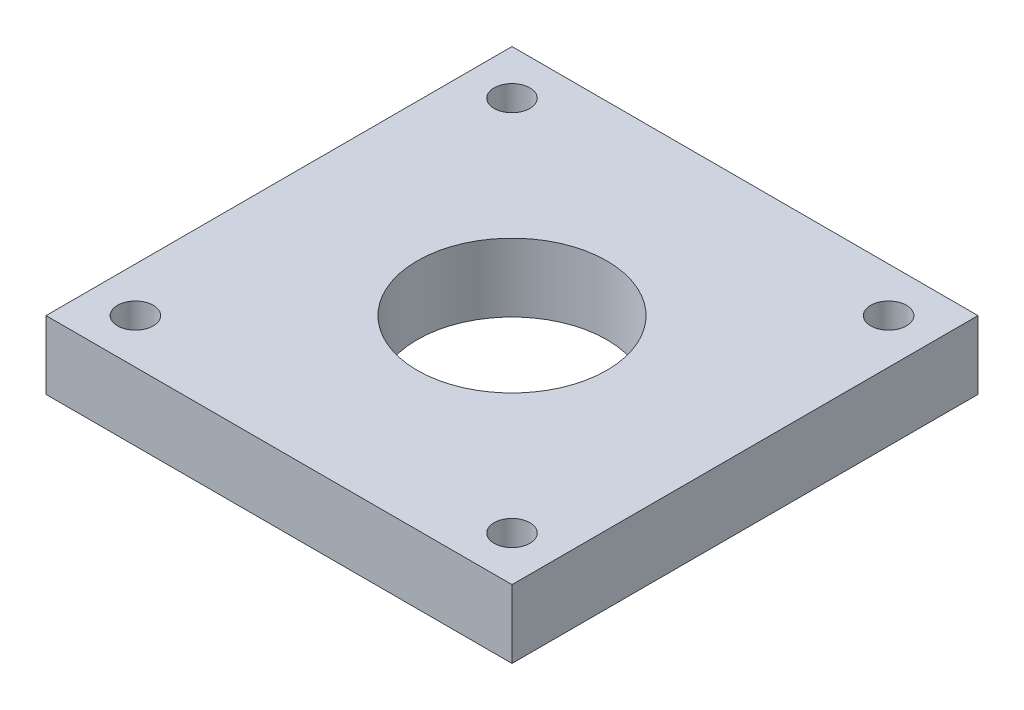
SolidWorks part; units mm, degrees
ref_plane "Front Plane" through (0, 0, 0) normal (0, 0, 1) x (1, 0, 0)
ref_plane "Top Plane" through (0, 0, 0) normal (0, 1, 0) x (1, 0, 0)
ref_plane "Right Plane" through (0, 0, 0) normal (1, 0, 0) x (0, 0, -1)
sketch "Sketch1" plane through (0, 0, 0) normal (0, 1, 0) x (1, 0, 0)
  line L1 (-43, 43) -> (43, 43)
  line L2 (-43, 43) -> (-43, -43)
  line L3 (-43, -43) -> (43, -43)
  line L4 (43, 43) -> (43, -43)
  line L5 (-43, 43) -> (43, -43) construction
  line L6 (-43, -43) -> (43, 43) construction
  circle A0 centre (0, 0) radius 17.5
  point P0 (0, 0)
  dimension "D3" = 35
  dimension "D1" = 86
  dimension "D2" = 86
extrude "Boss-Extrude1" add sketch "Sketch1" along normal blind 12.6
sketch "Sketch2" plane through (0, 12.6, 0) normal (0, 1, 0) x (1, 0, 0)
  circle A0 centre (-34.75, -34.75) radius 3.3 construction
  circle A1 centre (-34.75, 34.75) radius 3.3 construction
  circle A2 centre (34.75, -34.75) radius 3.3 construction
  circle A3 centre (34.75, 34.75) radius 3.3 construction
  circle A4 centre (-34.75, -34.75) radius 3.3
  circle A5 centre (-34.75, 34.75) radius 3.3
  circle A6 centre (34.75, -34.75) radius 3.3
  circle A7 centre (34.75, 34.75) radius 3.3
extrude "Cut-Extrude1" cut sketch "Sketch2" against normal up to next
